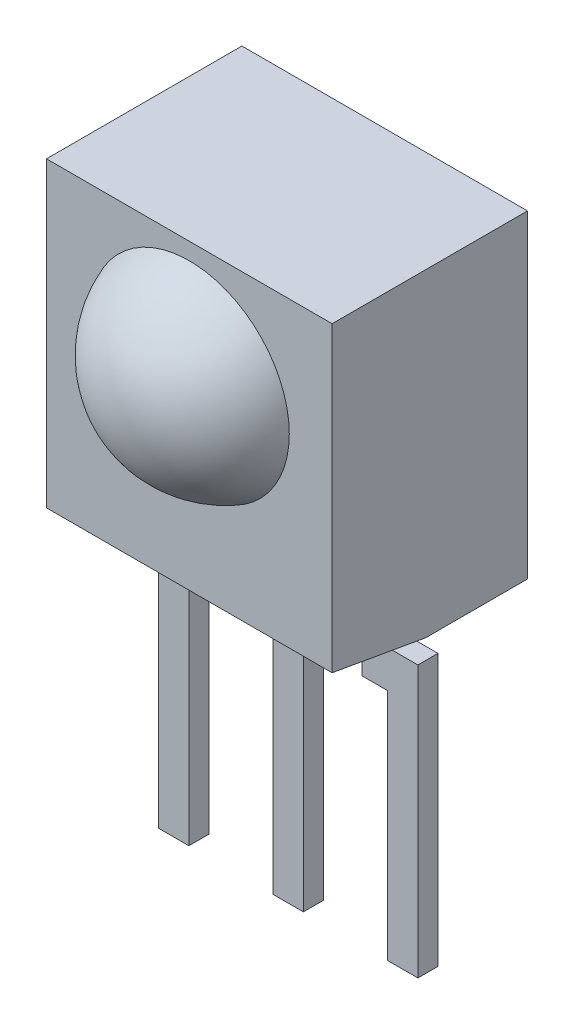
SolidWorks part; units mm, degrees
ref_plane "Front Plane" through (0, 0, 0) normal (0, 0, 1) x (1, 0, 0)
ref_plane "Top Plane" through (0, 0, 0) normal (0, 1, 0) x (1, 0, 0)
ref_plane "Right Plane" through (0, 0, 0) normal (1, 0, 0) x (0, 0, -1)
sketch "Sketch1" plane through (0, 0, 0) normal (0, 0, 1) x (1, 0, 0)
  line L1 (3.055, -3.41) -> (-3.055, -3.41)
  line L2 (3.055, -3.41) -> (3.055, 3.41)
  line L3 (3.055, 3.41) -> (-3.055, 3.41)
  line L4 (-3.055, -3.41) -> (-3.055, 3.41)
  line L5 (3.055, -3.41) -> (-3.055, 3.41) construction
  line L6 (3.055, 3.41) -> (-3.055, -3.41) construction
  point P0 (0, 0)
  dimension "D1" = 6.11
  dimension "D2" = 6.82
extrude "Boss-Extrude1" add sketch "Sketch1" along normal blind 4.18
sketch "Sketch3" plane through (0, 0, 0) normal (1, 0, 0) x (0, 0, -1)
  line L0 (-3.405, 3.185) -> (-3.405, -1.365)
  line L1 (-4.18, 3.41) -> (0, 3.41) construction
  line L2 (-4.18, -3.41) -> (-4.18, 3.41) construction
  arc A0 (-3.405, 3.185) -> (-3.405, -1.365) centre (-3.405, 0.91) ccw
  point P6 (-5.68, 0.91)
  dimension "D1" = 4.55
  dimension "D2" = 1.5
  dimension "2.5" = 2.5
revolve "Revolve1" add sketch "Sketch3" angle 360 about L0
sketch "Sketch4" plane through (0, -3.41, 0) normal (0, -1, 0) x (1, 0, 0)
  line L0 (-3.055, 1.85) -> (3.055, 1.85) construction
  line L1 (-3.055, 4.18) -> (-3.055, 0) construction
  line L2 (3.055, 4.18) -> (3.055, 0) construction
  line L3 (-3.055, 4.18) -> (3.055, 4.18) construction
  line L5 (0.325, 1.635) -> (-0.325, 1.635)
  line L6 (0.325, 1.635) -> (0.325, 2.065)
  line L7 (0.325, 2.065) -> (-0.325, 2.065)
  line L8 (-0.325, 1.635) -> (-0.325, 2.065)
  line L9 (0.325, 1.635) -> (-0.325, 2.065) construction
  line L10 (0.325, 2.065) -> (-0.325, 1.635) construction
  point P8 (0, 1.85)
  dimension "D1" = 2.33
  dimension "D2" = 0.43
  dimension "D3" = 0.65
extrude "Boss-Extrude2" add sketch "Sketch4" along normal blind 1.5
pattern_linear "LPattern1" count 2 spacing 1.9 along (1, 0, 0) count 2 spacing 1.9 along (-1, 0, 0) of "Boss-Extrude2" pattern seed only yes
sketch "Sketch5" plane through (-2.225, 0, 0) normal (-1, 0, 0) x (0, 0, 1)
  line L0 (2.065, -4.91) -> (2.065, -3.41) construction
  line L1 (1.635, -4.91) -> (2.065, -4.91)
  line L2 (1.635, -4.91) -> (1.635, -4.11)
  line L3 (1.635, -4.11) -> (2.065, -4.11)
  line L4 (2.065, -4.91) -> (2.065, -4.11)
  dimension "D1" = 0.8
extrude "Boss-Extrude3" add sketch "Sketch5" along normal blind 0.55
mirror "Mirror1" about plane through (0, 0, 0) normal (1, 0, 0) of "Boss-Extrude3"
ref_plane "Plane1" through (0, -27.09, 0) normal (0, 1, 0) x (1, 0, 0)
sketch "Sketch6" plane through (0, -4.91, 0) normal (0, -1, 0) x (1, 0, 0)
  line L0 (-1.575, 2.065) -> (-2.775, 2.065) construction
  line L1 (0.325, 1.635) -> (-0.325, 1.635)
  line L2 (0.325, 1.635) -> (0.325, 2.065)
  line L3 (0.325, 2.065) -> (-0.325, 2.065)
  line L4 (-0.325, 1.635) -> (-0.325, 2.065)
  line L5 (-2.775, 1.635) -> (-2.125, 1.635)
  line L6 (-2.775, 1.635) -> (-2.775, 2.065)
  line L7 (-2.775, 2.065) -> (-2.125, 2.065)
  line L8 (-2.125, 1.635) -> (-2.125, 2.065)
  line L9 (2.775, 2.065) -> (1.575, 2.065) construction
  line L10 (2.775, 1.635) -> (2.125, 1.635)
  line L11 (2.775, 1.635) -> (2.775, 2.065)
  line L12 (2.775, 2.065) -> (2.125, 2.065)
  line L13 (2.125, 1.635) -> (2.125, 2.065)
  dimension "D1" = 0.65
  dimension "D2" = 0.65
extrude "Boss-Extrude4" add sketch "Sketch6" along normal blind 5
chamfer "Chamfer1" distance 2 angle 10 1 edges at (0, -3.41, 4.18) first distance on face at (1.9, -3.41, 1.85)
